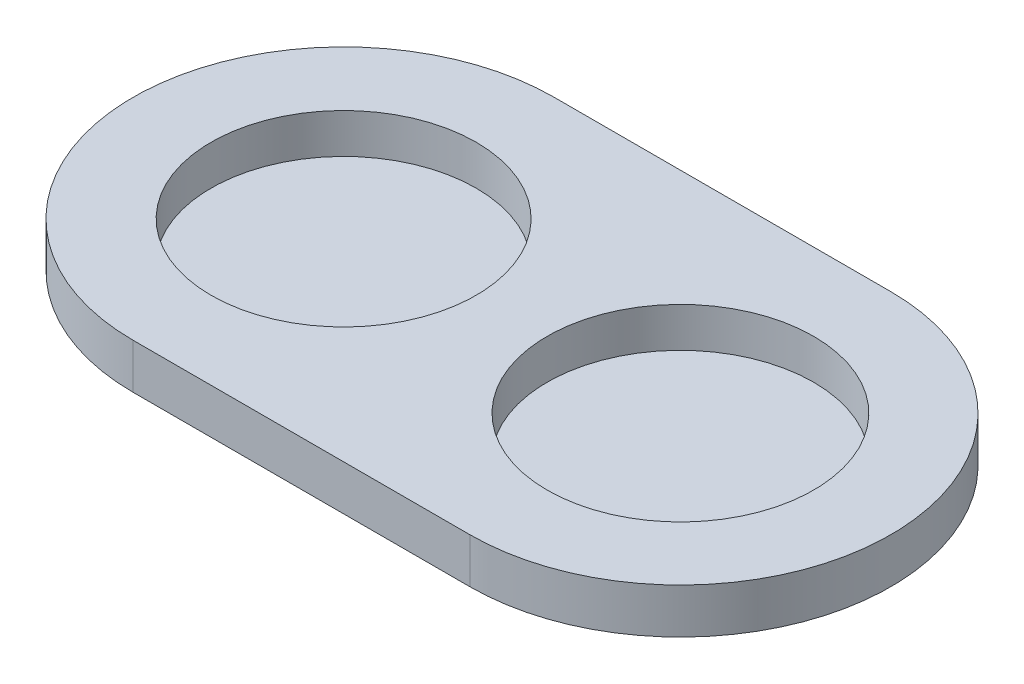
SolidWorks part; units mm, degrees
ref_plane "Front Plane" through (0, 0, 0) normal (0, 0, 1) x (1, 0, 0)
ref_plane "Top Plane" through (0, 0, 0) normal (0, 1, 0) x (1, 0, 0)
ref_plane "Right Plane" through (0, 0, 0) normal (1, 0, 0) x (0, 0, -1)
sketch "Sketch1" plane through (0, 0, 0) normal (0, 1, 0) x (1, 0, 0)
  line L0 (0, 0) -> (25.4, 0) construction
  line L1 (0, 15.875) -> (25.4, 15.875)
  line L2 (0, -15.875) -> (25.4, -15.875)
  arc A0 (0, 15.875) -> (0, -15.875) centre (0, 0) ccw
  arc A1 (25.4, -15.875) -> (25.4, 15.875) centre (25.4, 0) ccw
  circle A2 centre (0, 0) radius 10
  circle A3 centre (25.4, 0) radius 10.05
  point P3 (12.7, 0)
  dimension "D1" = 15.875
  dimension "D3" = 20
  dimension "D4" = 20.1
  dimension "D2" = 25.4
extrude "Boss-Extrude1" add sketch "Sketch1" along normal blind 3.4
extrude "Boss-Extrude2" add sketch "Sketch1<2>" along normal blind 0.4 contours A2 | A3 region at (0, 0, 0) region at (25.4, 0, 0)
sketch "Sketch1<2>" plane through (0, 0, 0) normal (0, 1, 0) x (1, 0, 0) same geometry as "Sketch1"
